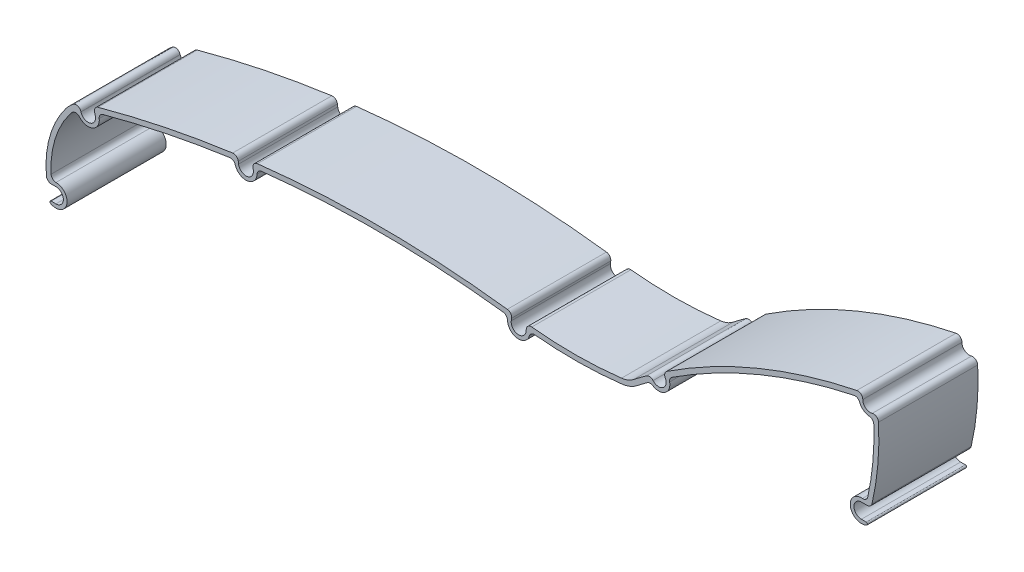
SolidWorks part; units mm, degrees
material "ｴﾎﾟｷｼ樹脂(充填剤なし)"
ref_plane "正面" through (0, 0, 0) normal (0, 0, 1) x (1, 0, 0)
ref_plane "平面" through (0, 0, 0) normal (0, 1, 0) x (1, 0, 0)
ref_plane "右側面" through (0, 0, 0) normal (1, 0, 0) x (0, 0, -1)
sketch "ｽｹｯﾁ1" plane through (0, 0, 0) normal (0, 0, 1) x (1, 0, 0)
  line L0 (152.9445, 59.7861) -> (155.8283, 58.959) construction
  line L2 (-22.5, -19) -> (22.5, -19)
  line L3 (147, 0) -> (148, 0)
  line L21 (148, 0) -> (148, 15)
  line L23 (148, 15) -> (147, 15)
  circle A0 centre (152.9445, 59.7861) radius 3 construction
  arc A25 (145.1533, 34.0834) -> (159.4857, 99.1473) centre (52.35, 88.6367) ccw
  arc A26 (159.4857, 99.1473) -> (155.9642, 101.8061) centre (156.5, 98.8544) ccw
  arc A27 (155.9642, 101.8061) -> (72.9103, 68.1854) centre (195.2577, -114.6564) ccw
  arc A28 (72.0597, 68.0608) -> (72.9103, 68.1854) centre (72.3541, 69.0165) ccw
  arc A29 (72.0597, 68.0608) -> (72.9103, 68.1854) centre (72.3541, 69.0165) ccw
  arc A30 (72.0597, 68.0608) -> (68.1825, 65.3859) centre (71.1764, 65.1938) ccw
  arc A31 (72.0597, 68.0608) -> (68.1825, 65.3859) centre (71.1764, 65.1938) ccw
  arc A32 (56.1841, 57.7039) -> (61.1056, 59.7088) centre (55.0078, 67.6345) ccw
  arc A33 (15.0718, 58.0612) -> (56.1841, 57.7039) centre (37.0313, 219.3955) ccw
  arc A34 (15.0718, 58.0612) -> (-159.8291, 45.3832) centre (-42.29, -363.3692) ccw
  arc A35 (-159.8291, 45.3832) -> (-168.029, 39.7531) centre (-155.4945, 30.2837) ccw
  arc A36 (-168.029, 39.7531) -> (-174.9177, 6.802) centre (-136.5587, 15.9784) ccw
  arc A37 (-174.9177, 6.802) -> (-172, 4.5) centre (-172, 7.5) ccw
  arc A38 (-128.5711, -10.4869) -> (-172, 4.5) centre (-172, -65.9175) ccw
  arc A39 (-128.5711, -10.4869) -> (-89, -16.1206) centre (-103.9017, 21) ccw
  arc A40 (-24.2684, -18.5879) -> (-89, -16.1206) centre (-59.3978, -89.8605) ccw
  arc A41 (-24.2684, -18.5879) -> (-22.5, -19) centre (-22.5, -15) ccw
  arc A42 (95.4808, -24.1793) -> (22.5, -19) centre (22.5, -535.7727) ccw
  arc A43 (95.4808, -24.1793) -> (100, -24.5) centre (100, 7.5) ccw
  arc A44 (100, -24.5) -> (140.9896, -3.1331) centre (100, 25.5) ccw
  arc A45 (147, 0) -> (140.9896, -3.1331) centre (147, -7.3316) ccw
  arc A48 (67.7641, 64.635) -> (68.1825, 65.3859) centre (67.1846, 65.4499) ccw
  arc A49 (145.1533, 34.0834) -> (140.4977, 25.4404) centre (258.5173, -32.5563) ccw
  arc A50 (155.8283, 58.959) -> (159.4857, 99.1473) centre (52.35, 88.6367) ccw
  arc A51 (159.4857, 99.1473) -> (155.9642, 101.8061) centre (156.5, 98.8544) ccw
  arc A52 (155.9642, 101.8061) -> (72.9103, 68.1854) centre (195.2577, -114.6564) ccw
  arc A53 (67.7641, 64.635) -> (68.1825, 65.3859) centre (67.1846, 65.4499) ccw
  arc A54 (67.7641, 64.635) -> (61.1056, 59.7088) centre (195.2577, -114.6564) ccw
  arc A55 (67.7641, 64.635) -> (61.1056, 59.7088) centre (195.2577, -114.6564) ccw
  arc A56 (140.4977, 25.4404) -> (147, 15) centre (147, 22.245) ccw
  arc A57 (56.1841, 57.7039) -> (61.1056, 59.7088) centre (55.0078, 67.6345) ccw
  arc A58 (15.0718, 58.0612) -> (56.1841, 57.7039) centre (37.0313, 219.3955) ccw
  arc A59 (15.0718, 58.0612) -> (-159.8291, 45.3832) centre (-42.29, -363.3692) ccw
  arc A60 (-159.8291, 45.3832) -> (-168.029, 39.7531) centre (-155.4945, 30.2837) ccw
  arc A61 (-168.029, 39.7531) -> (-174.9177, 6.802) centre (-136.5587, 15.9784) ccw
  dimension "D1" = 0
extrude "押し出し-薄板1" add sketch "ｽｹｯﾁ1" along normal up to surface (40 mm away) thin thin type one direction reverse wall 2
sketch "ｽｹｯﾁ2" plane through (0, 0, 0) normal (0, 0, 1) x (1, 0, 0)
  circle A0 centre (156.5, 98.8544) radius 3 construction
  circle A1 centre (152.9445, 59.7861) radius 3 construction
  circle A2 centre (71.1764, 65.1938) radius 3 construction
  circle A3 centre (14.6672, 55.0886) radius 3 construction
  circle A4 centre (-95.3328, 55.6027) radius 3 construction
  circle A5 centre (-159, 42.5) radius 3 construction
  circle A6 centre (-172, 7.5) radius 3 construction
  circle A7 centre (156.5, 98.8544) radius 3
  circle A8 centre (152.9445, 59.7861) radius 3
  circle A9 centre (71.1764, 65.1938) radius 3
  circle A10 centre (14.6672, 55.0886) radius 3
  circle A11 centre (-95.3328, 55.6027) radius 3
  circle A12 centre (-159, 42.5) radius 3
  circle A13 centre (-172, 7.5) radius 3
extrude "ﾎﾞｽ - 押し出し1" add sketch "ｽｹｯﾁ2" along normal through all
sketch "ｽｹｯﾁ3" plane through (0, 0, 40) normal (0, 0, 1) x (1, 0, 0)
  circle A0 centre (-172, 7.5) radius 4.5
  circle A1 centre (-159, 42.5) radius 4.5
  circle A2 centre (-95.3328, 55.6027) radius 4.5
  circle A3 centre (14.6672, 55.0886) radius 4.5
  circle A4 centre (71.1764, 65.1938) radius 4.5
  circle A5 centre (156.5, 98.8544) radius 4.5
  circle A6 centre (152.9445, 59.7861) radius 4.5
  arc A37 (-168.029, 39.7531) -> (-174.9177, 6.802) centre (-136.5587, 15.9784) ccw
  arc A38 (-174.9177, 6.802) -> (-173.5323, 10.0791) centre (-172, 7.5) ccw
  arc A39 (-166.4332, 38.5475) -> (-173.5323, 10.0791) centre (-136.5587, 15.9784) ccw
  arc A40 (-161.9964, 42.3531) -> (-166.4332, 38.5475) centre (-155.4945, 30.2837) ccw
  arc A41 (-161.9964, 42.3531) -> (-156.5523, 44.2345) centre (-159, 42.5) ccw
  arc A42 (-98.2666, 56.2298) -> (-156.5523, 44.2345) centre (-42.29, -363.3692) ccw
  arc A43 (-98.2666, 56.2298) -> (-92.6479, 56.9411) centre (-95.3328, 55.6027) ccw
  arc A44 (11.9949, 56.452) -> (-92.6479, 56.9411) centre (-42.29, -363.3692) ccw
  arc A45 (11.9949, 56.452) -> (17.5993, 55.723) centre (14.6672, 55.0886) ccw
  arc A46 (17.5993, 55.723) -> (56.4194, 55.7178) centre (37.0313, 219.3955) ccw
  arc A47 (56.4194, 55.7178) -> (62.3252, 58.1237) centre (55.0078, 67.6345) ccw
  arc A48 (68.9231, 63.005) -> (62.3252, 58.1237) centre (195.2577, -114.6564) ccw
  arc A49 (68.9231, 63.005) -> (69.0373, 63.0904) centre (67.1846, 65.4499) ccw
  arc A50 (69.0373, 63.0904) -> (73.9022, 66.4467) centre (71.1764, 65.1938) ccw
  arc A51 (73.9022, 66.4467) -> (74.0225, 66.5232) centre (72.3541, 69.0165) ccw
  arc A52 (153.5354, 99.3138) -> (74.0225, 66.5232) centre (195.2577, -114.6564) ccw
  arc A53 (153.5354, 99.3138) -> (157.7346, 96.1202) centre (156.5, 98.8544) ccw
  arc A54 (154.6525, 62.2525) -> (157.7346, 96.1202) centre (52.35, 88.6367) ccw
  arc A55 (154.6525, 62.2525) -> (155.8283, 58.959) centre (152.9445, 59.7861) ccw
  arc A56 (155.8283, 58.959) -> (159.4857, 99.1473) centre (52.35, 88.6367) ccw
  arc A57 (159.4857, 99.1473) -> (155.9642, 101.8061) centre (156.5, 98.8544) ccw
  arc A58 (155.9642, 101.8061) -> (72.9103, 68.1854) centre (195.2577, -114.6564) ccw
  arc A59 (72.0597, 68.0608) -> (72.9103, 68.1854) centre (72.3541, 69.0165) ccw
  arc A60 (72.0597, 68.0608) -> (68.1825, 65.3859) centre (71.1764, 65.1938) ccw
  arc A61 (67.7641, 64.635) -> (68.1825, 65.3859) centre (67.1846, 65.4499) ccw
  arc A62 (67.7641, 64.635) -> (61.1056, 59.7088) centre (195.2577, -114.6564) ccw
  arc A63 (56.1841, 57.7039) -> (61.1056, 59.7088) centre (55.0078, 67.6345) ccw
  arc A64 (15.0718, 58.0612) -> (56.1841, 57.7039) centre (37.0313, 219.3955) ccw
  arc A65 (15.0718, 58.0612) -> (-159.8291, 45.3832) centre (-42.29, -363.3692) ccw
  arc A66 (-159.8291, 45.3832) -> (-168.029, 39.7531) centre (-155.4945, 30.2837) ccw
  arc A67 (-168.029, 39.7531) -> (-174.9177, 6.802) centre (-136.5587, 15.9784) ccw
  arc A68 (-174.9177, 6.802) -> (-173.5323, 10.0791) centre (-172, 7.5) ccw
  arc A69 (-166.4332, 38.5475) -> (-173.5323, 10.0791) centre (-136.5587, 15.9784) ccw
  arc A70 (-161.9964, 42.3531) -> (-166.4332, 38.5475) centre (-155.4945, 30.2837) ccw
  arc A71 (-161.9964, 42.3531) -> (-156.5523, 44.2345) centre (-159, 42.5) ccw
  arc A72 (-98.2666, 56.2298) -> (-156.5523, 44.2345) centre (-42.29, -363.3692) ccw
  arc A73 (-98.2666, 56.2298) -> (-92.6479, 56.9411) centre (-95.3328, 55.6027) ccw
  arc A74 (11.9949, 56.452) -> (-92.6479, 56.9411) centre (-42.29, -363.3692) ccw
  arc A75 (11.9949, 56.452) -> (17.5993, 55.723) centre (14.6672, 55.0886) ccw
  arc A76 (17.5993, 55.723) -> (56.4194, 55.7178) centre (37.0313, 219.3955) ccw
  arc A77 (56.4194, 55.7178) -> (62.3252, 58.1237) centre (55.0078, 67.6345) ccw
  arc A78 (68.9231, 63.005) -> (62.3252, 58.1237) centre (195.2577, -114.6564) ccw
  arc A79 (68.9231, 63.005) -> (69.0373, 63.0904) centre (67.1846, 65.4499) ccw
  arc A80 (69.0373, 63.0904) -> (73.9022, 66.4467) centre (71.1764, 65.1938) ccw
  arc A81 (73.9022, 66.4467) -> (74.0225, 66.5232) centre (72.3541, 69.0165) ccw
  arc A82 (153.5354, 99.3138) -> (74.0225, 66.5232) centre (195.2577, -114.6564) ccw
  arc A83 (153.5354, 99.3138) -> (157.7346, 96.1202) centre (156.5, 98.8544) ccw
  arc A84 (154.6525, 62.2525) -> (157.7346, 96.1202) centre (52.35, 88.6367) ccw
  arc A85 (154.6525, 62.2525) -> (155.8283, 58.959) centre (152.9445, 59.7861) ccw
  arc A86 (155.8283, 58.959) -> (159.4857, 99.1473) centre (52.35, 88.6367) ccw
  arc A87 (159.4857, 99.1473) -> (155.9642, 101.8061) centre (156.5, 98.8544) ccw
  arc A88 (155.9642, 101.8061) -> (72.9103, 68.1854) centre (195.2577, -114.6564) ccw
  arc A89 (72.0597, 68.0608) -> (72.9103, 68.1854) centre (72.3541, 69.0165) ccw
  arc A90 (72.0597, 68.0608) -> (68.1825, 65.3859) centre (71.1764, 65.1938) ccw
  arc A91 (67.7641, 64.635) -> (68.1825, 65.3859) centre (67.1846, 65.4499) ccw
  arc A92 (67.7641, 64.635) -> (61.1056, 59.7088) centre (195.2577, -114.6564) ccw
  arc A93 (56.1841, 57.7039) -> (61.1056, 59.7088) centre (55.0078, 67.6345) ccw
  arc A94 (15.0718, 58.0612) -> (56.1841, 57.7039) centre (37.0313, 219.3955) ccw
  arc A95 (15.0718, 58.0612) -> (-159.8291, 45.3832) centre (-42.29, -363.3692) ccw
  arc A96 (-159.8291, 45.3832) -> (-168.029, 39.7531) centre (-155.4945, 30.2837) ccw
  arc M31 (-168.029, 39.7531) -> (-174.9177, 6.802) centre (-136.5587, 15.9784) ccw
  arc M32 (-174.9177, 6.802) -> (-173.5323, 10.0791) centre (-172, 7.5) ccw
  arc M33 (-173.5323, 10.0791) -> (-166.4332, 38.5475) centre (-136.5587, 15.9784) cw
  arc M34 (-166.4332, 38.5475) -> (-161.9964, 42.3531) centre (-155.4945, 30.2837) cw
  arc M35 (-161.9964, 42.3531) -> (-156.5523, 44.2345) centre (-159, 42.5) ccw
  arc M36 (-156.5523, 44.2345) -> (-98.2666, 56.2298) centre (-42.29, -363.3692) cw
  arc M37 (-98.2666, 56.2298) -> (-92.6479, 56.9411) centre (-95.3328, 55.6027) ccw
  arc M38 (-92.6479, 56.9411) -> (11.9949, 56.452) centre (-42.29, -363.3692) cw
  arc M39 (11.9949, 56.452) -> (17.5993, 55.723) centre (14.6672, 55.0886) ccw
  arc M40 (17.5993, 55.723) -> (56.4194, 55.7178) centre (37.0313, 219.3955) ccw
  arc M42 (62.3252, 58.1237) -> (68.9231, 63.005) centre (195.2577, -114.6564) cw
  arc M43 (68.9231, 63.005) -> (69.0373, 63.0904) centre (67.1846, 65.4499) ccw
  arc M44 (69.0373, 63.0904) -> (73.9022, 66.4467) centre (71.1764, 65.1938) ccw
  arc M45 (73.9022, 66.4467) -> (74.0225, 66.5232) centre (72.3541, 69.0165) ccw
  arc M46 (74.0225, 66.5232) -> (153.5354, 99.3138) centre (195.2577, -114.6564) cw
  arc M47 (153.5354, 99.3138) -> (157.7346, 96.1202) centre (156.5, 98.8544) ccw
  arc M48 (157.7346, 96.1202) -> (154.6525, 62.2525) centre (52.35, 88.6367) cw
  arc M49 (154.6525, 62.2525) -> (155.8283, 58.959) centre (152.9445, 59.7861) ccw
  arc M50 (155.8283, 58.959) -> (159.4857, 99.1473) centre (52.35, 88.6367) ccw
  dimension "D1" = 9
  dimension "D2" = 0
extrude "ﾎﾞｽ - 押し出し2" add sketch "ｽｹｯﾁ3" against normal through all contours A6 M48 M50 M49 | A5 M46 M48 M47 | A4 M42 M46 M45 M44 M43 | A3 M38 M40 M39 | A2 M36 M38 M37 | A1 M34 M36 M35 | A0 M31 M33 M32 region at (-173.3991, 3.3572, 40) region at (-162.6457, 41.8498, 40) region at (-99.0256, 56.0185, 40) region at (11.207, 56.4437, 40) region at (68.4255, 62.5239, 40) region at (154.5686, 96.3204, 40) region at (154.7218, 63.0426, 40)
sketch "ｽｹｯﾁ4" plane through (0, 0, 40) normal (0, 0, 1) x (1, 0, 0)
  line L0 (-159, 42.5) -> (-159.8361, 45.3811) construction
  line L1 (-161.8811, 41.6639) -> (-162.7173, 44.545)
  line L2 (-156.1189, 43.3361) -> (-156.955, 46.2173)
  line L3 (-172, 7.5) -> (-176.5, 7.5) construction
  line L4 (-172, 4.5) -> (-176.5, 4.5)
  line L5 (-172, 10.5) -> (-176.5, 10.5)
  line L6 (-95.3328, 55.6027) -> (-95.7096, 58.579) construction
  line L7 (-98.3091, 55.2259) -> (-98.6859, 58.2022)
  line L8 (-92.3566, 55.9795) -> (-92.7334, 58.9558)
  line L9 (14.6672, 55.0886) -> (15.0718, 58.0612) construction
  line L10 (11.6946, 55.4932) -> (12.0992, 58.4658)
  line L11 (17.6397, 54.684) -> (18.0444, 57.6566)
  line L12 (71.1764, 65.1938) -> (69.4728, 67.6631) construction
  line L13 (68.707, 63.4901) -> (67.0034, 65.9595)
  line L14 (73.6457, 66.8974) -> (71.9421, 69.3667)
  line L15 (156.5, 98.8544) -> (158.3077, 101.2486) construction
  line L16 (154.1058, 100.6621) -> (155.9135, 103.0563)
  line L17 (158.8942, 97.0467) -> (160.7019, 99.4409)
  line L18 (152.9445, 59.7861) -> (157.4445, 59.7861) construction
  line L19 (152.9445, 62.7861) -> (157.4445, 62.7861)
  line L20 (152.9445, 56.7861) -> (157.4445, 56.7861)
  line L21 (-99.8134, 56.0205) -> (-91.0978, 57.1239) construction
  arc A0 (15.0718, 58.0612) -> (-159.8291, 45.3832) centre (-42.29, -363.3692) ccw construction
  arc A1 (-159.8291, 45.3832) -> (-168.029, 39.7531) centre (-155.4945, 30.2837) ccw construction
  arc A2 (-161.8811, 41.6639) -> (-156.1189, 43.3361) centre (-159, 42.5) ccw
  arc A3 (-156.955, 46.2173) -> (-162.7173, 44.545) centre (-159.8361, 45.3811) ccw
  arc A4 (-172, 4.5) -> (-172, 10.5) centre (-172, 7.5) ccw
  arc A5 (-176.5, 10.5) -> (-176.5, 4.5) centre (-176.5, 7.5) ccw
  arc A6 (-98.3091, 55.2259) -> (-92.3566, 55.9795) centre (-95.3328, 55.6027) ccw
  arc A7 (-92.7334, 58.9558) -> (-98.6859, 58.2022) centre (-95.7096, 58.579) ccw
  arc A8 (15.0718, 58.0612) -> (56.1841, 57.7039) centre (37.0313, 219.3955) ccw construction
  arc A9 (11.6946, 55.4932) -> (17.6397, 54.684) centre (14.6672, 55.0886) ccw
  arc A10 (18.0444, 57.6566) -> (12.0992, 58.4658) centre (15.0718, 58.0612) ccw
  arc A11 (72.0597, 68.0608) -> (68.1825, 65.3859) centre (71.1764, 65.1938) ccw construction
  arc A12 (68.707, 63.4901) -> (73.6457, 66.8974) centre (71.1764, 65.1938) ccw
  arc A13 (71.9421, 69.3667) -> (67.0034, 65.9595) centre (69.4728, 67.6631) ccw
  arc A14 (159.4857, 99.1473) -> (155.9642, 101.8061) centre (156.5, 98.8544) ccw construction
  arc A15 (154.1058, 100.6621) -> (158.8942, 97.0467) centre (156.5, 98.8544) ccw
  arc A16 (160.7019, 99.4409) -> (155.9135, 103.0563) centre (158.3077, 101.2486) ccw
  arc A17 (155.0325, 63.7724) -> (156.7143, 62.2434) centre (152.9445, 59.7861) ccw construction
  arc A18 (152.9445, 62.7861) -> (152.9445, 56.7861) centre (152.9445, 59.7861) ccw
  arc A19 (157.4445, 56.7861) -> (157.4445, 62.7861) centre (157.4445, 59.7861) ccw
  arc A20 (-175.5786, 10.2283) -> (-173.7486, 11.6464) centre (-172, 7.5) ccw construction
  point P12 (-159.4181, 43.9406)
  point P19 (-174.25, 7.5)
  point P29 (-95.5212, 57.0909)
  point P37 (14.8695, 56.5749)
  point P48 (70.3246, 66.4284)
  point P59 (157.4039, 100.0515)
  point P70 (155.1945, 59.7861)
  dimension "D1" = 6
extrude "ｶｯﾄ - 押し出し2" cut sketch "ｽｹｯﾁ4" against normal through all
fillet "ﾌｨﾚｯﾄ1" radius 2 24 edges at (-173.7486, 11.6464, 20) (-155.0485, 44.6531, 20) (-99.8134, 56.0205, 20) (-91.0978, 57.1239, 20) (10.4465, 56.6493, 20) (19.1437, 55.5471, 20) (67.8096, 62.208, 20) (75.163, 67.2811, 20) (152.0027, 99.0092, 20) (157.834, 94.5566, 20) (155.0325, 63.7724, 20) (156.8501, 62.7861, 20) (159.5943, 97.9739, 20) (154.8088, 101.5932, 20) (72.801, 68.1218, 20) (67.8623, 64.7146, 20) (18.048, 57.684, 20) (12.0977, 58.4553, 20) (-92.7321, 58.9453, 20) (-98.6846, 58.1917, 20) (-156.95, 46.2001, 20) (-162.6387, 44.2745, 20) (-175.6177, 10.5, 20) (-163.3861, 41.4939, 20)
fillet "ﾌｨﾚｯﾄ2" radius 0.5 2 edges at (156.2986, 56.7861, 20) (-175.3541, 4.5, 20)
